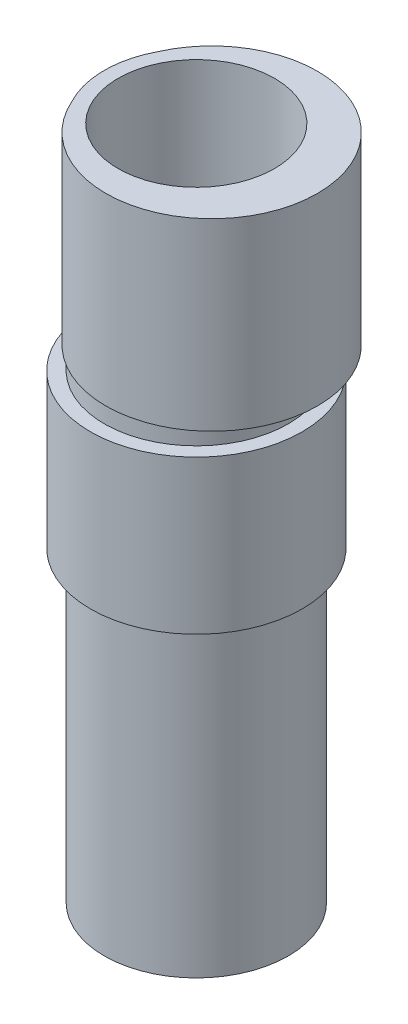
SolidWorks part; units mm, degrees
ref_plane "Front Plane" through (0, 0, 0) normal (0, 0, 1) x (1, 0, 0)
ref_plane "Top Plane" through (0, 0, 0) normal (0, 1, 0) x (1, 0, 0)
ref_plane "Right Plane" through (0, 0, 0) normal (1, 0, 0) x (0, 0, -1)
sketch "Sketch1" plane through (0, 0, 0) normal (0, 1, 0) x (1, 0, 0)
  circle A0 centre (0, 0) radius 3.45
  dimension "D1" = 6.9
extrude "Boss-Extrude1" add sketch "Sketch1" along normal blind 6
sketch "Sketch2" plane through (0, -4.98, 0) normal (0, -1, 0) x (1, 0, 0)
  line L0 (0, 0) -> (-0.5, 0) construction
  circle A0 centre (-0.5, 0) radius 3.45
  dimension "D1" = 6.9
extrude "Boss-Extrude2" add sketch "Sketch2" against normal blind 4 and the other way blind 1
sketch "Sketch3" plane through (0, 6, 0) normal (0, 1, 0) x (1, 0, 0)
  circle A0 centre (-0.5, 0) radius 3
  dimension "D1" = 6
extrude "Boss-Extrude4" add sketch "Sketch3" against normal blind 22
sketch "Sketch4" plane through (0, -16, 0) normal (0, -1, 0) x (1, 0, 0)
  line L0 (0, 0) -> (-0.5, 0)
  circle A0 centre (-0.5, 0) radius 2.55
  dimension "D1" = 5.1
extrude "Cut-Extrude1" cut sketch "Sketch4" against normal through all contours A0
